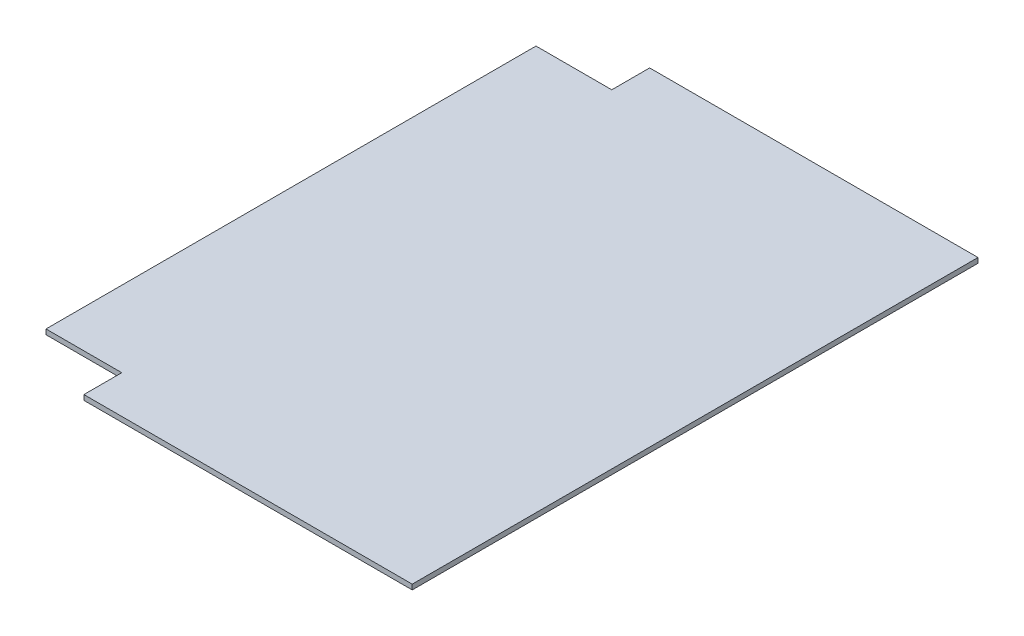
SolidWorks part; units mm, degrees
ref_plane "Front Plane" through (0, 0, 0) normal (0, 0, 1) x (1, 0, 0)
ref_plane "Top Plane" through (0, 0, 0) normal (0, 1, 0) x (1, 0, 0)
ref_plane "Right Plane" through (0, 0, 0) normal (1, 0, 0) x (0, 0, -1)
sketch "Sketch1" plane through (0, 0, 0) normal (0, 1, 0) x (1, 0, 0)
  line L1 (-80, 112) -> (80, 112)
  line L2 (-80, 112) -> (-80, -112)
  line L3 (-80, -112) -> (80, -112)
  line L4 (80, 112) -> (80, -112)
  line L5 (-80, 112) -> (80, -112) construction
  line L6 (-80, -112) -> (80, 112) construction
  point P0 (0, 0)
  dimension "D1" = 224
  dimension "D2" = 160
extrude "Boss-Extrude1" add sketch "Sketch1" along normal mid plane 2
sketch "Sketch41" plane through (0, 1, 0) normal (0, 1, 0) x (1, 0, 0)
  line L0 (-1.1, 0) -> (1.1, 0) construction
  line L1 (-80, -112) -> (-50, -112)
  line L2 (-80, -112) -> (-80, -97)
  line L3 (-80, -97) -> (-50, -97)
  line L4 (-50, -112) -> (-50, -97)
  line L5 (-80, 97) -> (-50, 97)
  line L6 (-50, 112) -> (-50, 97)
  line L7 (-80, 112) -> (-50, 112)
  line L8 (-80, 112) -> (-80, 97)
  dimension "D1" = 30
  dimension "D2" = 15
extrude "Cut-Extrude2" cut sketch "Sketch41" against normal blind 40
